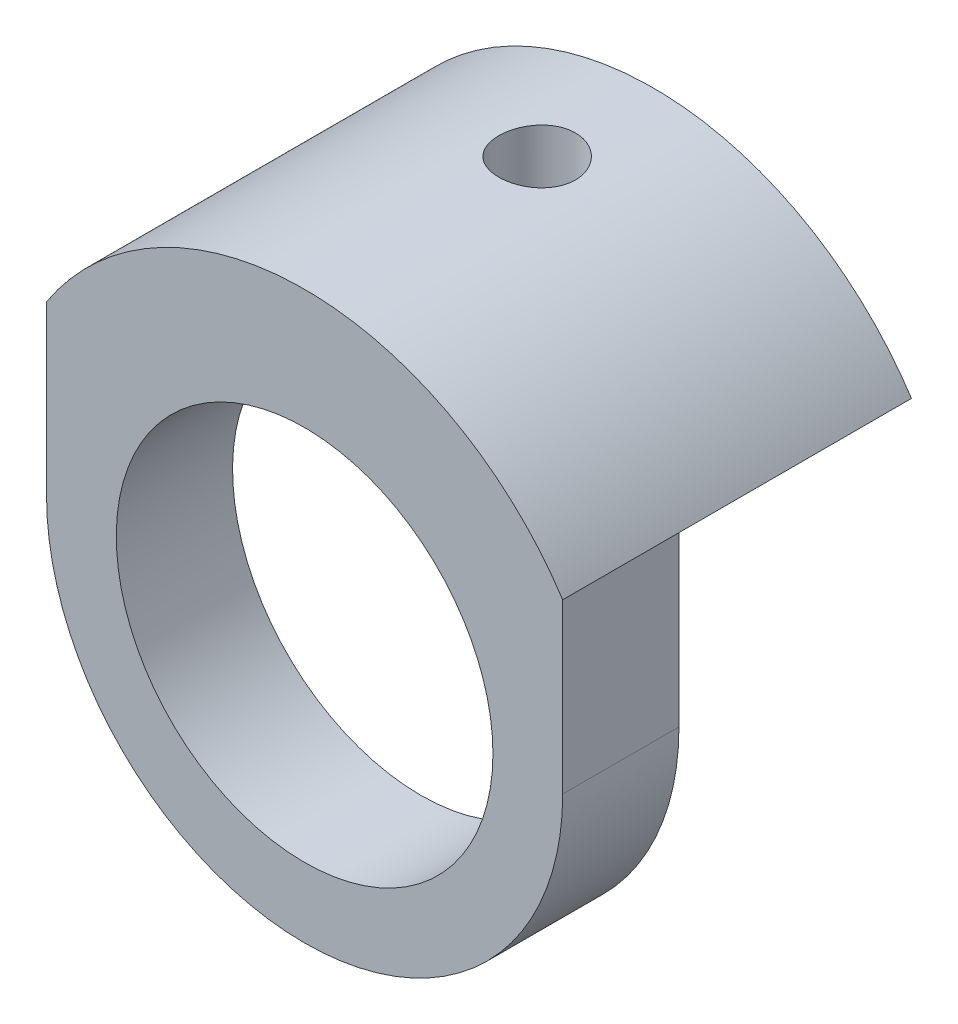
SolidWorks part; units mm, degrees
ref_plane "Front Plane" through (0, 0, 0) normal (0, 0, 1) x (1, 0, 0)
ref_plane "Top Plane" through (0, 0, 0) normal (0, 1, 0) x (1, 0, 0)
ref_plane "Right Plane" through (0, 0, 0) normal (1, 0, 0) x (0, 0, -1)
sketch "Sketch1" plane through (0, 0, 0) normal (0, 0, 1) x (1, 0, 0)
  line L0 (-11.1, 0) -> (11.1, 0)
  line L1 (-11.1, 0) -> (-11.1, 7.2355)
  line L2 (11.1, 0) -> (11.1, 7.2355)
  circle A0 centre (0, 0) radius 8.1
  circle A1 centre (0, 0) radius 13.25
  circle A2 centre (0, 0) radius 11.1
  point P5 (0, 0)
  dimension "16.2" = 16.2
  dimension "D2" = 26.5
  dimension "D3" = 3
extrude "Boss-Extrude1" add sketch "Sketch1" along normal blind 15 contours L0 A2 A0 | A2 L2 A1 L1 | L0 A2 A0 region at (0, 8.3482, 0) region at (9.6, -0.2482, 0) region at (0, 11.3585, 0)
sketch "Sketch2" plane through (-11.1, 0, 0) normal (-1, 0, 0) x (0, 0, 1)
  line L0 (15, 0) -> (15, 7.2355) construction
  line L1 (0, 7.2355) -> (10, 7.2355)
  line L2 (0, 7.2355) -> (0, -11.1)
  line L3 (0, -11.1) -> (10, -11.1)
  line L4 (10, 7.2355) -> (10, -11.1)
  dimension "D1" = 5
extrude "Cut-Extrude1" cut sketch "Sketch2" against normal up to surface (22.2 mm away) up to face at (11.1, 3.6178, 7.5)
sketch "Sketch3" plane through (0, 7.2355, 0) normal (0, -1, 0) x (1, 0, 0)
  line L0 (-3.6411, 0) -> (3.6411, 0) construction
  circle A0 centre (0, 5) radius 1.65
  dimension "D1" = 3.3
  dimension "D2" = 5
extrude "Cut-Extrude2" cut sketch "Sketch3" against normal up to surface (5.9114 mm away) up to face at (0, 9.2403, 8.3333)
sketch "Sketch4" plane through (0, 7.2355, 0) normal (0, -1, 0) x (1, 0, 0)
  line L0 (-3.6411, 0) -> (3.6411, 0) construction
  line L1 (1.5877, 7.75) -> (-1.5877, 7.75)
  line L2 (-1.5877, 7.75) -> (-3.1754, 5)
  line L3 (-3.1754, 5) -> (-1.5877, 2.25)
  line L4 (-1.5877, 2.25) -> (1.5877, 2.25)
  line L5 (1.5877, 2.25) -> (3.1754, 5)
  line L6 (3.1754, 5) -> (1.5877, 7.75)
  circle A0 centre (0, 5) radius 2.75 construction
  dimension "D1" = 5.5
extrude "Cut-Extrude3" cut sketch "Sketch4" against normal blind 3
